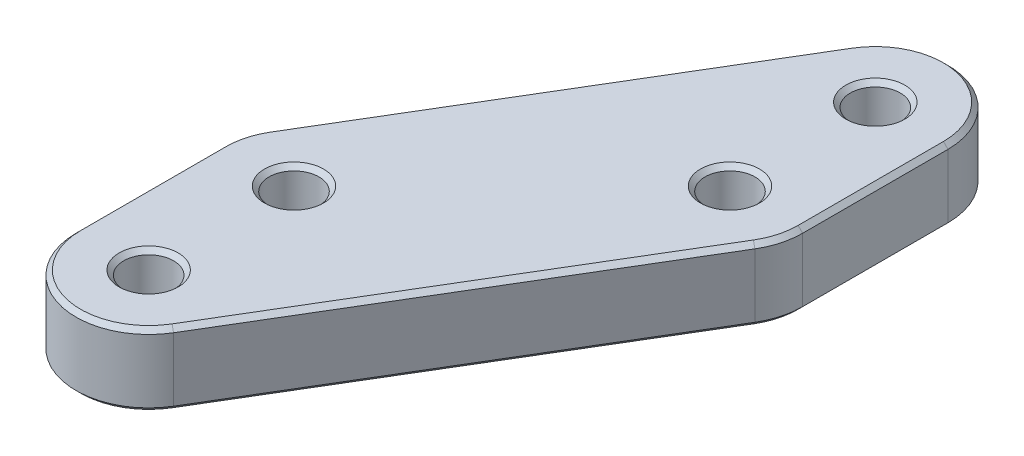
SolidWorks part; units mm, degrees
ref_plane "Front Plane" through (0, 0, 0) normal (0, 0, 1) x (1, 0, 0)
ref_plane "Top Plane" through (0, 0, 0) normal (0, 1, 0) x (1, 0, 0)
ref_plane "Right Plane" through (0, 0, 0) normal (1, 0, 0) x (0, 0, -1)
sketch "Sketch1" plane through (0, 0, 0) normal (0, 1, 0) x (1, 0, 0)
  line L0 (-25.4, -19.05) -> (-25.4, -31.75)
  line L1 (5.4451, -3.267) -> (-13.6049, -35.017)
  line L2 (-24.4951, -15.783) -> (-5.4451, 15.967)
  line L4 (6.35, 0) -> (6.35, 12.7)
  circle A0 centre (0, 0) radius 2.1828
  circle A1 centre (0, 12.7) radius 2.1828
  circle A2 centre (-19.05, -19.05) radius 2.1828
  circle A3 centre (-19.05, -31.75) radius 2.1828
  arc A4 (-25.4, -31.75) -> (-13.6049, -35.017) centre (-19.05, -31.75) ccw
  arc A5 (-24.4951, -15.783) -> (-25.4, -19.05) centre (-19.05, -19.05) ccw
  arc A6 (5.4451, -3.267) -> (6.35, 0) centre (0, 0) ccw
  arc A7 (6.35, 12.7) -> (-5.4451, 15.967) centre (0, 12.7) ccw
  dimension "D2" = 4.3656
  dimension "D3" = 4.3656
  dimension "D6" = 4.3656
  dimension "D8" = 4.3656
  dimension "D9" = 12.7
  dimension "D10" = 12.7
  dimension "D11" = 12.7
  dimension "D12" = 12.7
  dimension "D1" = 12.7
  dimension "D4" = 19.05
  dimension "D5" = 19.05
  dimension "D7" = 12.7
extrude "Boss-Extrude1" add sketch "Sketch1" along normal mid plane 6.35
chamfer "Chamfer1" distance 0.3969 angle 45 24 edges at (-19.05, -3.175, 33.9328) (-19.05, -3.175, 21.2328) (0, -3.175, -10.5172) (0, -3.175, 2.1828) (-25.4, -3.175, 25.4) (-20.745, -3.175, 37.8696) (-4.0799, -3.175, 19.142) (6.1196, -3.175, 1.695) (1.695, -3.175, -18.8196) (-14.9701, -3.175, -0.092) (-25.1696, -3.175, 17.355) (-19.05, 3.175, 33.9328) (0, 3.175, -10.5172) (-14.9701, 3.175, -0.092) (1.695, 3.175, -18.8196) (6.1196, 3.175, 1.695) (-4.0799, 3.175, 19.142) (-20.745, 3.175, 37.8696) (-25.4, 3.175, 25.4) (-25.1696, 3.175, 17.355) (0, 3.175, 2.1828) (-19.05, 3.175, 21.2328) (6.35, -3.175, -6.35) (6.35, 3.175, -6.35)
